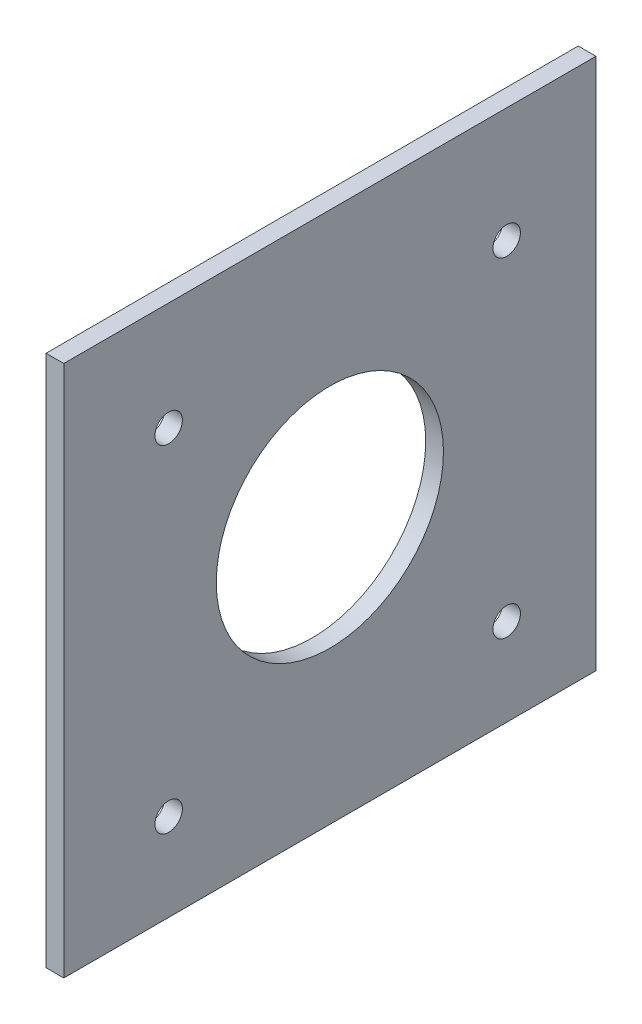
SolidWorks part; units mm, degrees
ref_plane "Front" through (0, 0, 0) normal (0, 0, 1) x (1, 0, 0)
ref_plane "Top" through (0, 0, 0) normal (0, 1, 0) x (1, 0, 0)
ref_plane "Right" through (0, 0, 0) normal (1, 0, 0) x (0, 0, -1)
sketch "Sketch1" plane through (0, 0, 0) normal (1, 0, 0) x (0, 0, -1)
  line L1 (47.625, -47.625) -> (-47.625, -47.625)
  line L2 (47.625, -47.625) -> (47.625, 47.625)
  line L3 (47.625, 47.625) -> (-47.625, 47.625)
  line L4 (-47.625, -47.625) -> (-47.625, 47.625)
  line L5 (47.625, -47.625) -> (-47.625, 47.625) construction
  line L6 (47.625, 47.625) -> (-47.625, -47.625) construction
  circle A0 centre (0, 0) radius 20.3289
  dimension "D1" = 40.6577
  dimension "D2" = 95.25
  dimension "D3" = 95.25
extrude "Boss-Extrude1" add sketch "Sketch1" along normal blind 3.175
sketch "Sketch4" plane through (3.175, 0, 0) normal (1, 0, 0) x (0, 0, -1)
  line L0 (-47.625, 47.625) -> (-47.625, -47.625) construction
  point P0 (-28.8538, 28.2555)
  point P2 (31.6461, 27.0588)
  point P4 (31.6461, -31.9785)
  point P6 (-28.8538, -31.9785)
  point P11 (0, 0)
  point P12 (0, 0)
  point P13 (0, 0)
  point P14 (0, 0)
  point P15 (0, 0)
  dimension "D1" = 18.7712
hole_wizard "#10 (0.1935) Diameter Hole1" positions "Sketch4" profile "Sketch3" hole size "#10" standard "ANSI Inch" end condition up to next
sketch "Sketch3" plane through (3.175, 28.2555, 28.8538) normal (0, 1, 0) x (0, 0, -1)
  line L0 (0, 0) -> (0, 3.175)
  line L1 (0, 3.175) -> (2.4574, 3.175)
  line L2 (2.4574, 3.175) -> (2.4574, 0)
  line L5 (2.4574, 0) -> (0, 0)
  line L11 (0, -6.35) -> (0, 107.95) construction
  dimension "Thru Hole Dia." = 4.9149
  dimension "Thru Hole Depth" = 3.175
